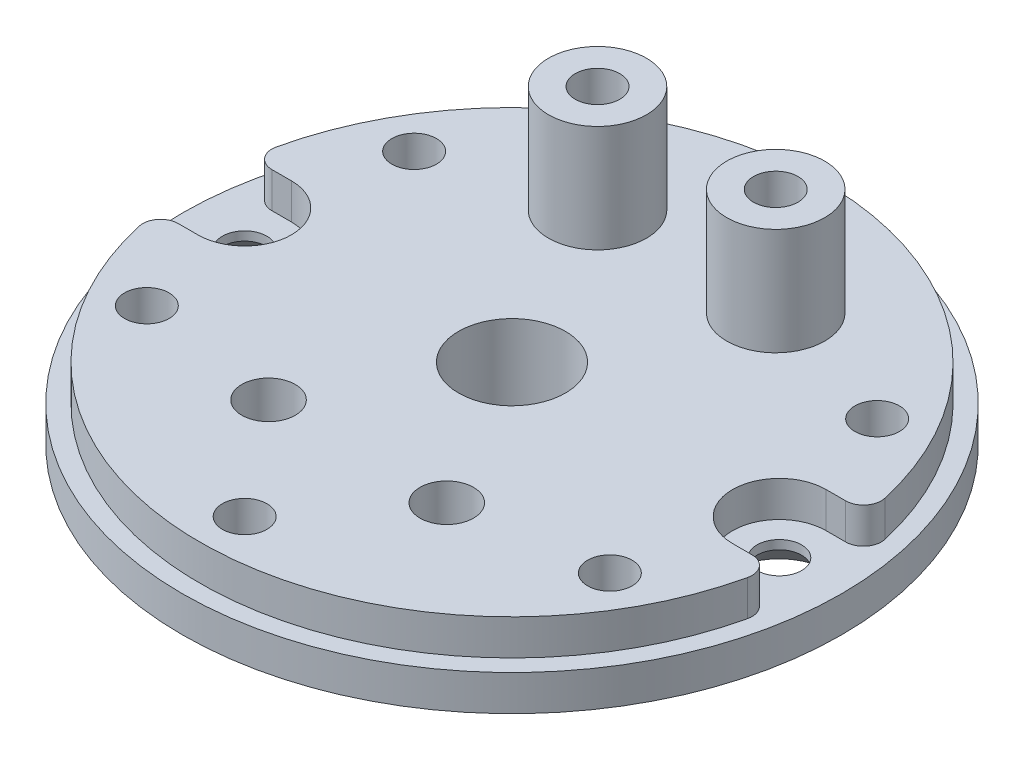
SolidWorks part; units mm, degrees
material "AISI 1020 Steel, Cold Rolled"
ref_plane "Front" through (0, 0, 0) normal (0, 0, 1) x (1, 0, 0)
ref_plane "Top" through (0, 0, 0) normal (0, 1, 0) x (1, 0, 0)
ref_plane "Right" through (0, 0, 0) normal (1, 0, 0) x (0, 0, -1)
sketch "Sketch1" plane through (0, 0, 0) normal (0, 1, 0) x (1, 0, 0)
  circle A0 centre (0, 0) radius 18.5
  dimension "D1" = 37
extrude "Boss-Extrude1" add sketch "Sketch1" along normal blind 2
sketch "Sketch2" plane through (0, 2, 0) normal (0, 1, 0) x (1, 0, 0)
  circle A0 centre (0, 0) radius 17.5
  dimension "D1" = 35
extrude "Boss-Extrude2" add sketch "Sketch2" along normal blind 2
sketch "Sketch3" plane through (0, 0, 0) normal (0, -1, 0) x (1, 0, 0)
  circle A0 centre (0, 0) radius 6
  dimension "D1" = 12
extrude "Boss-Extrude3" add sketch "Sketch3" along normal offset from surface (5 mm away) 9 up to face at (0, 4, 17.5)
sketch "Sketch4" plane through (0, -5, 0) normal (0, -1, 0) x (1, 0, 0)
  circle A0 centre (0, 0) radius 3
  dimension "D1" = 6
extrude "Cut-Extrude1" cut sketch "Sketch4" against normal up to next
sketch "Sketch5" plane through (0, 4, 0) normal (0, 1, 0) x (1, 0, 0)
  line L0 (-15, 2.625) -> (-17.625, 2.625)
  line L1 (-17.625, 2.625) -> (-17.625, -2.625)
  line L2 (-17.625, -2.625) -> (-15, -2.625)
  circle A0 centre (-15, 0) radius 2.625
  point P2 (-17.625, 2.6484)
  circle M5 centre (0, 0) radius 17.5
  dimension "D1" = 5.25
  dimension "D3" = 15
extrude "Cut-Extrude4" cut sketch "Sketch5" against normal up to surface (2 mm away) contours A0 M5 | A0 M5 | A0 L0 M5 | A0 L0 L1 M5 | A0 L2 M5 | A0 L1 L2 M5 region at (-16.8439, 4, -2.1587) region at (-14.9828, 4, 0) region at (-17.5162, 4, -1.7445) region at (-17.5458, 4, 0) region at (-16.8439, 4, 2.1587) region at (-17.5162, 4, 1.7445) up to face at (0, 2, 17.5)
fillet "Fillet1" radius 1 2 edges at (-17.302, 3, 2.625) (-17.302, 3, -2.625)
sketch "Sketch6" plane through (0, 2, 0) normal (0, 1, 0) x (1, 0, 0)
  circle A0 centre (-15, 0) radius 1.25
  arc A1 (-15, -2.625) -> (-15, 2.625) centre (-15, 0) ccw construction
  dimension "D1" = 2.5
extrude "Cut-Extrude5" cut sketch "Sketch6" against normal up to next
mirror "Mirror1" about plane through (0, 0, 0) normal (1, 0, 0) of "Cut-Extrude5", "Cut-Extrude4", "Fillet1"
chamfer "Chamfer1" distance 1.5 angle 45 2 edges at (15, 0, 1.25) (-15, 0, 1.25)
sketch "Sketch7" plane through (0, 0, 0) normal (0, -1, 0) x (1, 0, 0)
  circle A0 centre (0, 15) radius 1.25
  point P2 (0, 0)
  dimension "D1" = 2.5
  dimension "D2" = 15
extrude "Cut-Extrude6" cut sketch "Sketch7" against normal up to next
pattern_circular "CirPattern1" count 6 over 360 about axis through (0, -5, 0) along (0, -1, 0) of "Cut-Extrude6"
sketch "Sketch9" plane through (0, 4, 0) normal (0, 1, 0) x (1, 0, 0)
  circle A0 centre (-5, -8.6603) radius 1.5
  circle A1 centre (5, -8.6603) radius 1.5
  point P7 (1.4607, -3.3648)
  dimension "D4" = 3
  dimension "D1" = 10
  dimension "D2" = 10
  dimension "D3" = 10
extrude "Cut-Extrude7" cut sketch "Sketch9" against normal blind 3.5 contours A0 | A1 region at (-5, 4, 8.6603) region at (5, 4, 8.6603)
sketch "Sketch10" plane through (0, 4, 0) normal (0, 1, 0) x (1, 0, 0)
  circle A0 centre (-5, 9.798) radius 2.75
  circle A1 centre (5, 9.798) radius 2.75
  dimension "D4" = 5.5
  dimension "D1" = 10
  dimension "D2" = 11
  dimension "D3" = 11
extrude "Boss-Extrude4" add sketch "Sketch10" along normal offset from surface (6 mm away) 10 up to face at (11.9078, 0, 6.875)
sketch "Sketch11" plane through (0, 10, 0) normal (0, 1, 0) x (1, 0, 0)
  circle A0 centre (-5, 9.798) radius 1.25
  circle A1 centre (5, 9.798) radius 1.25
  dimension "D1" = 2.5
extrude "Cut-Extrude8" cut sketch "Sketch11" against normal up to surface (6 mm away) up to face at (5, 4, -7.048)
fillet "Fillet2" radius 0.25 2 edges at (0, 0, -6) (0, -5, 6)
chamfer "Chamfer2" distance 0.5 angle 45 1 edges at (0, -5, -3)
sketch "Sketch12" plane through (0, 0, 0) normal (0, -1, 0) x (1, 0, 0)
  line L0 (0, 0) -> (-15, 0) construction
  line L1 (0, 0) -> (0, 15) construction
  line L2 (-1.5, 12.9132) -> (-1.5, 7.3485) construction
  line L3 (-12.9132, 1.5) -> (-7.3485, 1.5) construction
  line L4 (-11.7367, 1.5) -> (-8.124, 1.5)
  line L5 (-1.5, 11.7367) -> (-1.5, 8.124)
  circle A0 centre (0, 0) radius 13 construction
  circle A1 centre (0, 0) radius 7.5 construction
  arc A2 (-12.7148, 2.7083) -> (-2.7083, 12.7148) centre (0, 0) cw
  arc A3 (-7.1683, 2.2059) -> (-2.2059, 7.1683) centre (0, 0) cw
  arc A4 (-1.5, 11.7367) -> (-2.7083, 12.7148) centre (-2.5, 11.7367) ccw
  arc A5 (-1.5, 8.124) -> (-2.2059, 7.1683) centre (-2.5, 8.124) cw
  arc A6 (-7.1683, 2.2059) -> (-8.124, 1.5) centre (-8.124, 2.5) cw
  arc A7 (-11.7367, 1.5) -> (-12.7148, 2.7083) centre (-11.7367, 2.5) cw
  dimension "D1" = 26
  dimension "D2" = 15
  dimension "D5" = 1
  dimension "D3" = 1.5
  dimension "D4" = 1.5
extrude "Cut-Extrude9" cut sketch "Sketch12" against normal blind 0.3
pattern_circular "CirPattern2" count 4 over 360 about axis through (0, 4.001, 0) along (0, -1, 0) of "Cut-Extrude9" reverse direction yes
chamfer "Chamfer3" distance 0.25 angle 45 6 edges at (-11.9078, 0, -6.875) (0, 0, -13.75) (11.9078, 0, -6.875) (11.9078, 0, 6.875) (-11.9078, 0, 6.875) (0, 0, 13.75)
